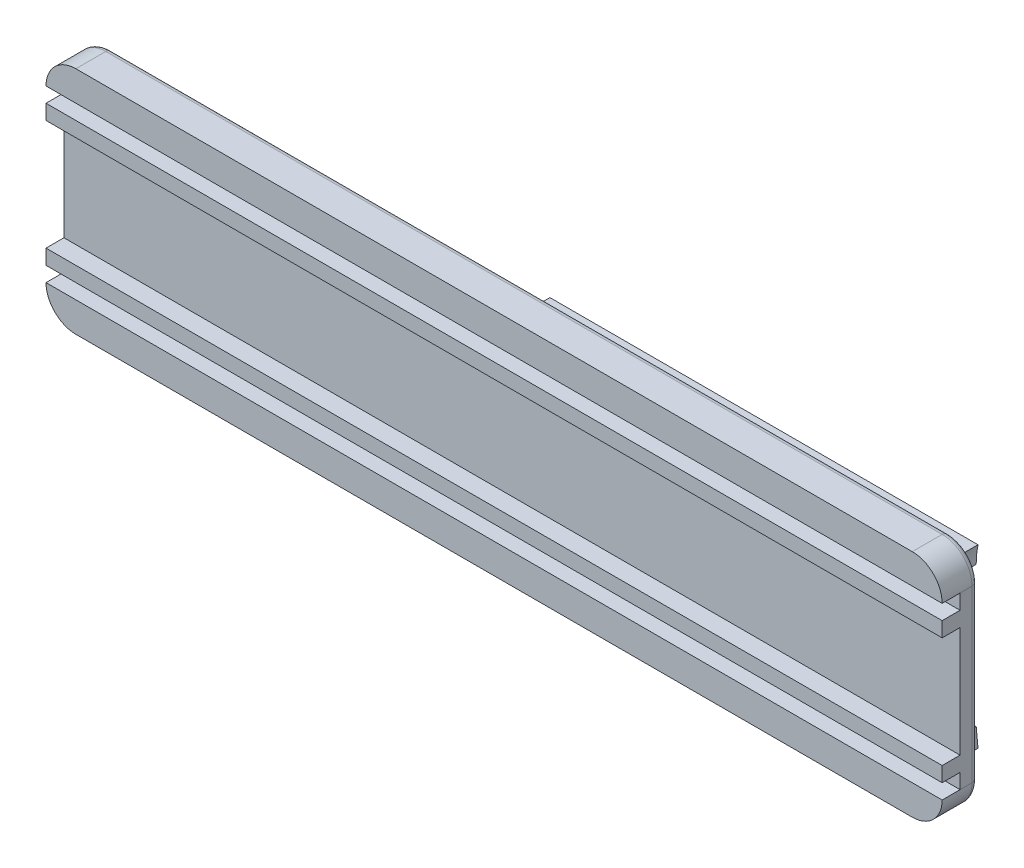
SolidWorks part; units mm, degrees
ref_plane "Ön Düzlem" through (0, 0, 0) normal (0, 0, 1) x (1, 0, 0)
ref_plane "Üst Düzlem" through (0, 0, 0) normal (0, 1, 0) x (1, 0, 0)
ref_plane "Sağ Düzlem" through (0, 0, 0) normal (1, 0, 0) x (0, 0, -1)
sketch "Çizim1" plane through (0, 0, 0) normal (0, 0, 1) x (1, 0, 0)
  line L2 (-92.7944, -56) -> (45.3965, -56)
  line L3 (-92.7944, -9) -> (45.3965, -9)
  line L4 (-92.7944, -9) -> (-97.3057, -9)
  line L5 (-97.3057, -9) -> (-97.3057, -3)
  line L6 (45.3965, -56) -> (46, -62)
  line L7 (-92.7944, -56) -> (-97.3057, -56)
  line L8 (-97.3057, -56) -> (-97.3057, -62)
  line L21 (-97.3057, -62) -> (46, -62)
  line L23 (46, -3) -> (-97.3057, -3)
  arc A0 (45.3965, -9) -> (46, -3) centre (75.5266, -9) cw
extrude "Yükseklik-Ekstrüzyon1" add sketch "Çizim1" along normal blind 10
sketch "Çizim2" plane through (0, 0, 10) normal (0, 0, 1) x (1, 0, 0)
  line L0 (-97.3057, -62) -> (46, -62) construction
  line L1 (56, 6) -> (-244, 6)
  line L2 (56, 6) -> (56, -71)
  line L3 (56, -71) -> (-244, -71)
  line L4 (-244, 6) -> (-244, -71)
  line L5 (46, -3) -> (-97.3057, -3) construction
  dimension "D1" = 9
  dimension "D2" = 9
  dimension "D3" = 300
  dimension "D4" = 10
extrude "Yükseklik-Ekstrüzyon2" add sketch "Çizim2" along normal blind 12
fillet "Radyus1" radius 10 4 edges at (56, -71, 16) (56, 6, 16) (-244, 6, 16) (-244, -71, 16)
sketch "Çizim3" plane through (0, 0, 22) normal (0, 0, 1) x (1, 0, 0)
  line L0 (-244, -4) -> (56, -4)
  line L1 (-244, -61) -> (56, -61)
  line L2 (-244, -14) -> (56, -14)
  line L3 (-244, -4) -> (-244, -61)
  line L4 (56, -61) -> (56, -4)
  line L5 (-244, -51) -> (56, -51)
  line M9 (-244, -4) -> (-244, -61)
  dimension "D1" = 10
  dimension "D2" = 10
extrude "Kes-Ekstrüzyon2" cut sketch "Çizim3" against normal blind 6 contours L5 L4 L2 M9 region at (-94, -32.5, 22)
sketch "Çizim4" plane through (0, 0, 22) normal (0, 0, 1) x (1, 0, 0)
  line L0 (-244, -56) -> (56, -56)
  line L1 (56, -56) -> (56, -61)
  line L2 (-244, -61) -> (56, -61)
  line L3 (-244, -4) -> (56, -4)
  line L4 (-244, -14) -> (56, -14)
  line L5 (56, -14) -> (56, -4)
  line L6 (46, 6) -> (-234, 6)
  line L7 (-244, -4) -> (-244, -14)
  line L8 (-244, -14) -> (56, -14)
  line L9 (56, -14) -> (56, -4)
  line L10 (46, 6) -> (-234, 6)
  line L11 (-244, -4) -> (-244, -14)
  line L12 (56, -61) -> (56, -51)
  line L13 (56, -51) -> (-244, -51)
  line L14 (-244, -51) -> (-244, -61)
  line L15 (-234, -71) -> (46, -71)
  line L16 (56, -61) -> (56, -51)
  line L17 (56, -51) -> (-244, -51)
  line L18 (-244, -51) -> (-244, -61)
  line L19 (-234, -71) -> (46, -71)
  line L20 (56, -9) -> (-244, -9)
  arc A2 (56, -4) -> (46, 6) centre (46, -4) ccw
  arc A3 (-234, 6) -> (-244, -4) centre (-234, -4) ccw
  arc A4 (56, -4) -> (46, 6) centre (46, -4) ccw
  arc A5 (-234, 6) -> (-244, -4) centre (-234, -4) ccw
  arc A6 (-244, -61) -> (-234, -71) centre (-234, -61) ccw
  arc A7 (46, -71) -> (56, -61) centre (46, -61) ccw
  arc A8 (-244, -61) -> (-234, -71) centre (-234, -61) ccw
  arc A9 (46, -71) -> (56, -61) centre (46, -61) ccw
  line M18 (-244, -4) -> (-244, -14)
  dimension "D1" = 0
  dimension "D2" = 0
extrude "Kes-Ekstrüzyon3" cut sketch "Çizim4" against normal blind 6 contours L20 L9 L3 M18 | L0 L18 L2 L1 region at (-94, -58.5, 22) region at (-94, -6.5, 22)
fillet "Radyus2" radius 2 8 edges at (-241.0711, -68.0711, 10) (-244, -32.5, 10) (-241.0711, 3.0711, 10) (-94, 6, 10) (53.0711, 3.0711, 10) (56, -32.5, 10) (53.0711, -68.0711, 10) (-94, -71, 10)
sketch "Çizim5" plane through (0, 0, 16) normal (0, 0, 1) x (1, 0, 0)
  line L4 (-244, -9) -> (56, -9)
  line L5 (56, -9) -> (56, -4)
  line L6 (56, -4) -> (-244, -4)
  line L7 (-244, -4) -> (-244, -9)
  line L8 (-244, -9) -> (56, -9)
  line L9 (56, -9) -> (56, -4)
  line L10 (56, -4) -> (-244, -4)
  line L11 (-244, -4) -> (-244, -9)
  line L12 (56, -56) -> (-244, -56)
  line L13 (-244, -56) -> (-244, -61)
  line L14 (-244, -61) -> (56, -61)
  line L15 (56, -61) -> (56, -56)
  line L16 (56, -56) -> (-244, -56)
  line L17 (-244, -56) -> (-244, -61)
  line L18 (-244, -61) -> (56, -61)
  line L19 (56, -61) -> (56, -56)
  dimension "D1" = 0
  dimension "D2" = 0
